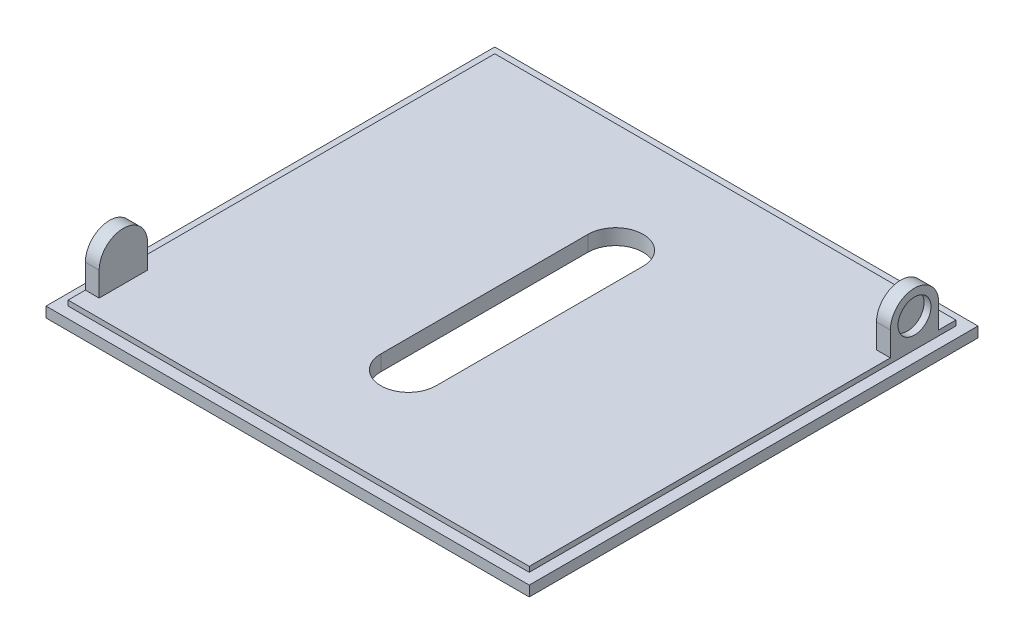
SolidWorks part; units mm, degrees
ref_plane "Front Plane" through (0, 0, 0) normal (0, 0, 1) x (1, 0, 0)
ref_plane "Top Plane" through (0, 0, 0) normal (0, 1, 0) x (1, 0, 0)
ref_plane "Right Plane" through (0, 0, 0) normal (1, 0, 0) x (0, 0, -1)
sketch "Sketch1" plane through (0, 0, 0) normal (0, 1, 0) x (1, 0, 0)
  line L1 (-70, 65) -> (70, 65)
  line L2 (-70, 65) -> (-70, -65)
  line L3 (-70, -65) -> (70, -65)
  line L4 (70, 65) -> (70, -65)
  line L5 (-70, 65) -> (70, -65) construction
  line L6 (-70, -65) -> (70, 65) construction
  point P0 (0, 0)
  dimension "D1" = 140
  dimension "D2" = 130
extrude "Boss-Extrude1" add sketch "Sketch1" along normal blind 3
sketch "Sketch2" plane through (0, 3, 0) normal (0, 1, 0) x (1, 0, 0)
  line L24 (66.8, -61.8) -> (66.8, 61.8)
  line L25 (-66.8, -61.8) -> (66.8, -61.8)
  line L26 (-66.8, 61.8) -> (-66.8, -61.8)
  line L27 (66.8, 61.8) -> (-66.8, 61.8)
  line L28 (66.8, -61.8) -> (66.8, 61.8)
  line L29 (-66.8, -61.8) -> (66.8, -61.8)
  line L30 (-66.8, 61.8) -> (-66.8, -61.8)
  line L31 (66.8, 61.8) -> (-66.8, 61.8)
  dimension "D1" = 3.2
extrude "Boss-Extrude2" add sketch "Sketch2" along normal blind 1.5
sketch "Sketch5" plane through (0, 4.5, 0) normal (0, 1, 0) x (1, 0, 0)
  line L0 (-66.8, 61.8) -> (-66.8, -61.8) construction
  line L1 (-66.8, -42.8) -> (-62.8, -42.8)
  line L2 (-66.8, -42.8) -> (-66.8, -56.8)
  line L3 (-66.8, -56.8) -> (-62.8, -56.8)
  line L4 (-62.8, -42.8) -> (-62.8, -56.8)
  line L5 (-66.8, 61.8) -> (-66.8, -61.8) construction
  line L6 (-66.8, -61.8) -> (66.8, -61.8) construction
  dimension "D1" = 4
  dimension "D2" = 14
  dimension "D3" = 5
extrude "Boss-Extrude3" add sketch "Sketch5" along normal blind 14
sketch "Sketch6" plane through (-66.8, 0, 0) normal (-1, 0, 0) x (0, 0, 1)
  line L0 (56.8, 18.5) -> (56.8, 4.5) construction
  line L1 (42.8, 18.5) -> (56.8, 18.5) construction
  circle A0 centre (49.8, 11.5) radius 4.775
  dimension "D1" = 9.55
  dimension "D2" = 7
  dimension "D3" = 7
extrude "Cut-Extrude3" cut sketch "Sketch6" against normal blind 2
fillet "Fillet1" 2 edges at (-64.8, 18.5, 56.8) (-64.8, 18.5, 42.8) type full round first side face at (-64.8, 11.5, 56.8) second side face at (-64.8, 11.5, 42.8) middle face at (-64.8, 18.5, 49.8)
ref_axis "Axis1" through (0, 19.425, 0) along (0, -1, 0)
pattern_circular "CirPattern2" count 2 every 180 about axis through (0, 19.425, 0) along (0, -1, 0) of "Boss-Extrude3", "Cut-Extrude3", "Fillet1"
sketch "Sketch7" plane through (0, 4.5, 0) normal (0, 1, 0) x (1, 0, 0)
  line L0 (0, -30) -> (0, 30) construction
  line L1 (-8, -30) -> (-8, 30)
  line L2 (8, -30) -> (8, 30)
  arc A0 (-8, -30) -> (8, -30) centre (0, -30) ccw
  arc A1 (8, 30) -> (-8, 30) centre (0, 30) ccw
  point P2 (0, 0)
  dimension "D2" = 8
  dimension "D1" = 60
extrude "Cut-Extrude4" cut sketch "Sketch7" against normal through all
